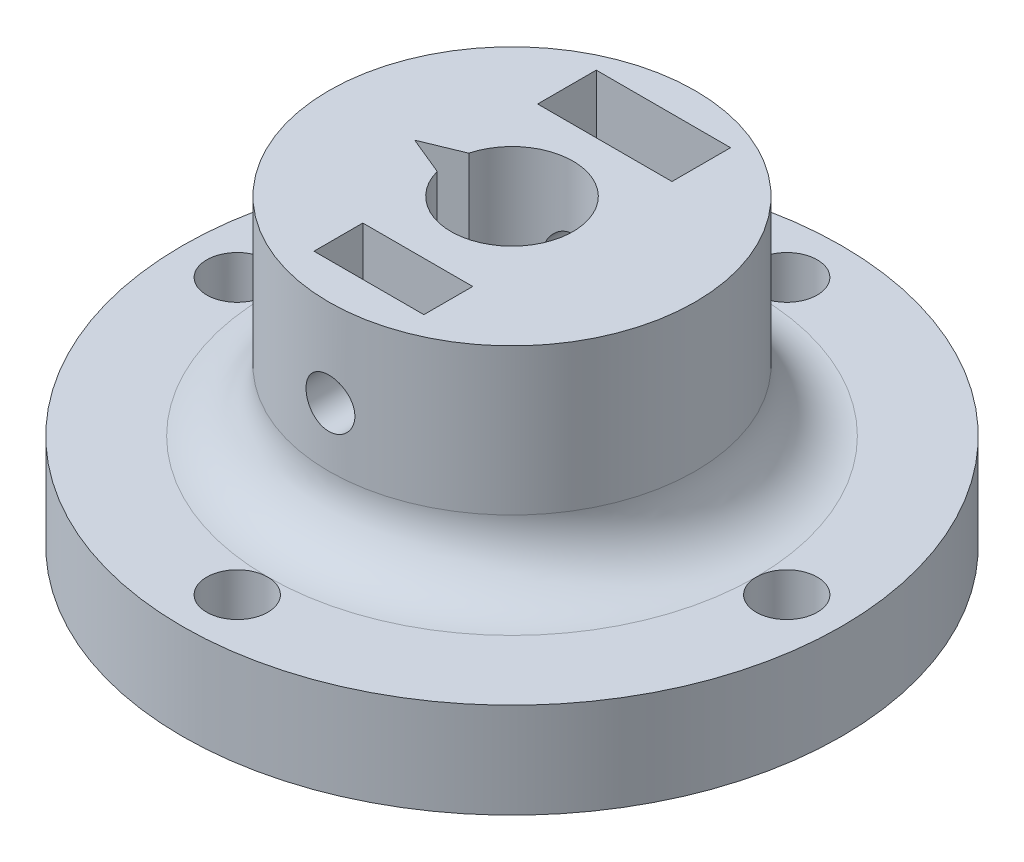
SolidWorks part; units mm, degrees
ref_plane "Front Plane" through (0, 0, 0) normal (0, 0, 1) x (1, 0, 0)
ref_plane "Top Plane" through (0, 0, 0) normal (0, 1, 0) x (1, 0, 0)
ref_plane "Right Plane" through (0, 0, 0) normal (1, 0, 0) x (0, 0, -1)
sketch "Sketch1" plane through (0, 0, 0) normal (0, 1, 0) x (1, 0, 0)
  line L1 (-5.963, -5.7013) -> (5.963, -5.7013)
  line L2 (-5.963, -5.7013) -> (-5.963, 5.7013)
  line L3 (-5.963, 5.7013) -> (5.963, 5.7013)
  line L4 (5.963, -5.7013) -> (5.963, 5.7013)
  line L5 (-5.963, -5.7013) -> (5.963, 5.7013) construction
  line L6 (-5.963, 5.7013) -> (5.963, -5.7013) construction
  circle A0 centre (0, 0) radius 13.5
  circle A6 centre (11.25, 0) radius 1.25
  circle A7 centre (0, -11.25) radius 1.25
  circle A8 centre (-11.25, 0) radius 1.25
  circle A9 centre (0, 11.25) radius 1.25
  point P23 (0, 0)
  dimension "D1" = 27
  dimension "D7" = 11.25
  dimension "D8" = 2.5
  dimension "D2" = 16.5
  dimension "D9" = 4
extrude "Boss-Extrude2" add sketch "Sketch1" along normal blind 2 contours A0 L4 L1 L2 L3 | L3 L2 L1 L4 region at (0, 0, 0) region at (-13.1182, 0, 0)
sketch "Sketch2" plane through (0, 2, 0) normal (0, 1, 0) x (1, 0, 0)
  circle A0 centre (0, 0) radius 7.5
  dimension "D1" = 15
extrude "Boss-Extrude3" add sketch "Sketch2" along normal blind 8.5
sketch "Sketch4" plane through (0, 10.5, 0) normal (0, 1, 0) x (1, 0, 0)
  circle A0 centre (0, 0) radius 2.5
  dimension "D1" = 5
extrude "Cut-Extrude1" cut sketch "Sketch4" against normal blind 7.5
sketch "Sketch5" plane through (0, 0, 0) normal (0, 0, 1) x (1, 0, 0)
  circle A0 centre (0, 6.9145) radius 1
  dimension "D1" = 2
extrude "Cut-Extrude2" cut sketch "Sketch5" against normal blind 11.75 and the other way blind 7.5
sketch "Sketch7" plane through (0, 0, 0) normal (0, -1, 0) x (1, 0, 0)
  circle A5 centre (0, 0) radius 5.25
  circle A11 centre (0, 0) radius 13.5
  point P0 (0, 0)
  dimension "D1" = 10.5
extrude "Boss-Extrude5" add sketch "Sketch7" along normal blind 1.9
sketch "Sketch9" plane through (0, 10.5, 0) normal (0, 1, 0) x (1, 0, 0)
  line L1 (-2.4148, -0.6473) -> (-2.4148, 0.6473)
  line L4 (-2.4148, 0.6473) -> (-3.9844, 0)
  line L5 (-3.9844, 0) -> (-2.4148, -0.6473)
  circle A1 centre (0, 0) radius 2.5 construction
  circle A2 centre (0, 0) radius 2.5 construction
extrude "Cut-Extrude3" cut sketch "Sketch9" against normal blind 8
fillet "Fillet1" radius 2.5 1 edges at (0, 2, 7.5)
sketch "Sketch12" plane through (0, 0, 0) normal (0, 1, 0) x (1, 0, 0)
  circle A0 centre (-0.2391, -10.0286) radius 0.0054
  circle A1 centre (-1.0146, 11.9661) radius 0.0081
  circle A2 centre (-11, 0) radius 1.25
  circle A3 centre (10.493, 0.9785) radius 0.0128
  dimension "D1" = 11
extrude "Cut-Extrude4" cut sketch "Sketch12" against normal blind 10
pattern_circular "CirPattern1" count 4 over 360 about axis through (0, 2, 0) along (0, 1, 0) of "Cut-Extrude4"
sketch "Sketch13" plane through (0, 10.5, 0) normal (0, 1, 0) x (1, 0, 0)
  line L1 (2.75, 6.2) -> (-2.75, 6.2)
  line L2 (2.75, 6.2) -> (2.75, 3.8)
  line L3 (2.75, 3.8) -> (-2.75, 3.8)
  line L4 (-2.75, 6.2) -> (-2.75, 3.8)
  line L5 (2.75, 6.2) -> (-2.75, 3.8) construction
  line L6 (2.75, 3.8) -> (-2.75, 6.2) construction
  line L7 (2.3917, -4) -> (-2.1083, -4)
  line L8 (2.3917, -4) -> (2.3917, -6)
  line L9 (2.3917, -6) -> (-2.1083, -6)
  line L10 (-2.1083, -4) -> (-2.1083, -6)
  line L11 (2.3917, -4) -> (-2.1083, -6) construction
  line L12 (2.3917, -6) -> (-2.1083, -4) construction
  point P0 (0, 5)
  point P5 (0.1417, -5)
  dimension "D1" = 5.5
  dimension "D2" = 2.4
  dimension "D3" = 0
  dimension "D4" = 5
  dimension "D5" = 2
  dimension "D6" = 4.5
  dimension "D7" = 5
extrude "Cut-Extrude5" cut sketch "Sketch13" against normal blind 4
sketch "Sketch14" plane through (0, 0, -3.8) normal (0, 0, -1) x (-1, 0, 0)
  line L1 (2.7218, 8.5501) -> (-0.0555, 10.0894)
  line L2 (-0.0555, 10.0894) -> (-2.7773, 8.4539)
  line L3 (-2.7773, 8.4539) -> (-2.7218, 5.279)
  line L4 (-2.7218, 5.279) -> (0.0555, 3.7396)
  line L5 (0.0555, 3.7396) -> (2.7773, 5.3751)
  line L6 (2.7773, 5.3751) -> (2.7218, 8.5501)
  circle A0 centre (0, 6.9145) radius 2.75 construction
  dimension "D1" = 5.5
extrude "Cut-Extrude6" cut sketch "Sketch14" along normal up to surface (2.4 mm away) up to face at (0, 8.0691, -6.2)
sketch "Sketch15" plane through (0, 0, 4) normal (0, 0, 1) x (1, 0, 0)
  line L0 (2.3917, 6.5) -> (2.3917, 10.5) construction
  line L1 (2.25, 8.2135) -> (0, 9.5126)
  line L2 (0, 9.5126) -> (-2.25, 8.2135)
  line L3 (-2.25, 8.2135) -> (-2.25, 5.6155)
  line L4 (-2.25, 5.6155) -> (0, 4.3164)
  line L5 (0, 4.3164) -> (2.25, 5.6155)
  line L6 (2.25, 5.6155) -> (2.25, 8.2135)
  circle A0 centre (0, 6.9145) radius 2.25 construction
  dimension "D1" = 4.5
  dimension "D2" = 180
extrude "Cut-Extrude7" cut sketch "Sketch15" along normal up to surface (2 mm away) up to face at (0.0945, 8.0691, 6)
